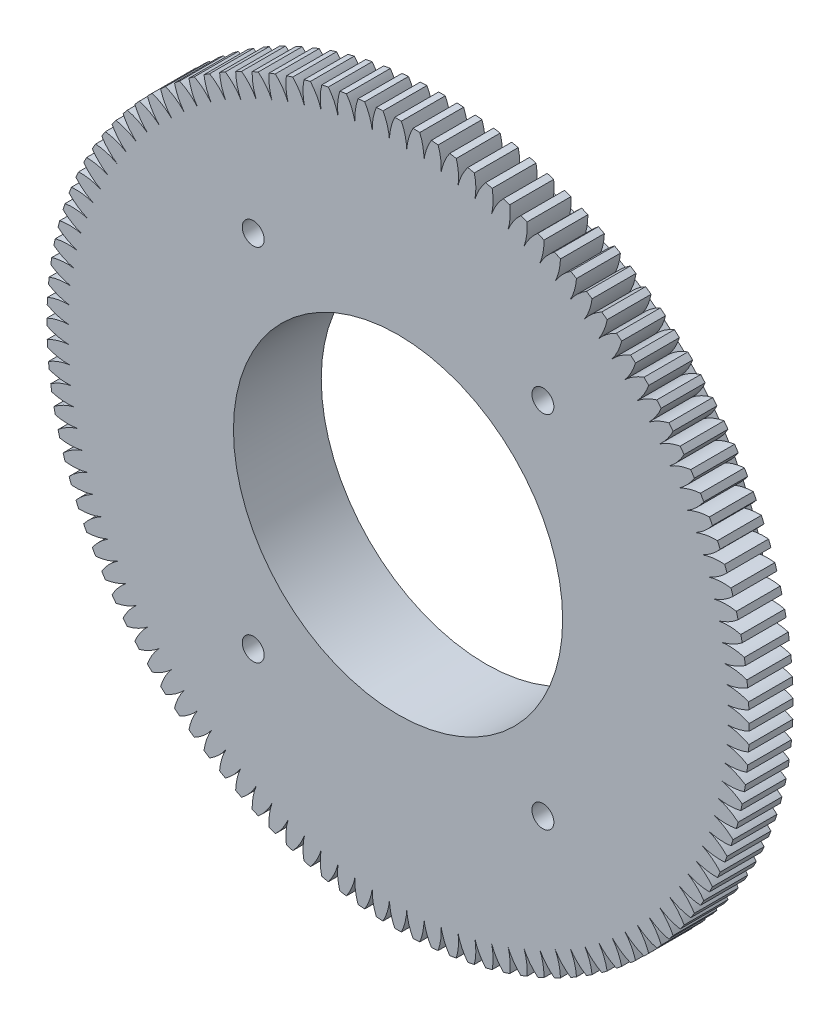
SolidWorks part; units mm, degrees
ref_plane "前视基准面" through (0, 0, 0) normal (0, 0, 1) x (1, 0, 0)
ref_plane "上视基准面" through (0, 0, 0) normal (0, 1, 0) x (1, 0, 0)
ref_plane "右视基准面" through (0, 0, 0) normal (1, 0, 0) x (0, 0, -1)
sketch "草图1" plane through (0, 0, 0) normal (0, 0, 1) x (1, 0, 0)
  circle A0 centre (0, 0) radius 75
  dimension "D1" = 150
extrude "凸台-拉伸1" add sketch "草图1" along normal blind 10
sketch "草图2" plane through (0, 0, 10) normal (0, 0, 1) x (1, 0, 0)
  line L1 (-33, -41) -> (33, -41) construction
  line L2 (-33, -41) -> (-33, 41) construction
  line L3 (-33, 41) -> (33, 41) construction
  line L4 (33, -41) -> (33, 41) construction
  line L5 (-33, -41) -> (33, 41) construction
  line L6 (-33, 41) -> (33, -41) construction
  point P0 (0, 0)
  dimension "D1" = 82
  dimension "D2" = 66
hole_wizard "M6 螺纹孔1" positions "草图3" profile "草图4" tap size "M6" standard "GB"
sketch "草图3" plane through (0, 0, 10) normal (0, 0, 1) x (1, 0, 0)
  point P0 (-33, 41)
  point P3 (33, 41)
  point P6 (33, -41)
  point P9 (-33, -41)
sketch "草图4" plane through (-33, 41, 10) normal (1, 0, 0) x (0, -1, 0)
  line L0 (0, 0) -> (0, 16.5022)
  line L1 (0, 16.5022) -> (2.5, 15)
  line L2 (2.5, 15) -> (2.5, 0)
  line L5 (2.5, 0) -> (0, 0)
  line L10 (0, 16.5022) -> (-2.5, 15) construction
  line L11 (0, -6.35) -> (0, 107.95) construction
  dimension "螺纹孔钻头直径" = 5
  dimension "螺纹孔钻头深度" = 15
  dimension "导头角度" = 118
cosmetic thread "孔螺纹线1" parameters "D1"=12, "D2"=6
cosmetic thread "孔螺纹线2" parameters "D1"=12, "D2"=6
cosmetic thread "孔螺纹线3" parameters "D1"=12, "D2"=6
cosmetic thread "孔螺纹线4" parameters "D1"=12, "D2"=6
sketch "草图5" plane through (0, 0, 10) normal (0, 0, 1) x (1, 0, 0)
  circle A0 centre (0, 0) radius 37.5
  dimension "D1" = 75
sketch "草图9" plane through (0, 0, 0) normal (0, 0, -1) x (-1, 0, 0)
  arc A5 (1.9633, 74.9743) -> (0.7613, 79.9964) centre (-10.3008, 74.6939) ccw
  arc A6 (-1.9633, 74.9743) -> (-0.7613, 79.9964) centre (10.3008, 74.6939) cw
  arc A7 (0.7613, 79.9964) -> (-0.7613, 79.9964) centre (0, 0) ccw
  circle A8 centre (0, 0) radius 75 construction
  arc A9 (1.9633, 74.9743) -> (-1.9633, 74.9743) centre (0, 0) ccw
extrude "凸台-拉伸2" add sketch "草图9" against normal blind 10
pattern_circular "阵列(圆周)1" count 120 over 360 about axis through (0, 0, 0) along (0, 0, 1) of "凸台-拉伸2"
sketch "草图11" plane through (0, 0, 0) normal (0, 0, -1) x (-1, 0, 0)
  circle A0 centre (0, 0) radius 70
  dimension "D1" = 140
sketch "草图13" plane through (0, 0, 0) normal (0, 0, -1) x (-1, 0, 0)
  circle A0 centre (0, 0) radius 65
  dimension "D1" = 130
extrude "凸台-拉伸3" add sketch "草图13" along normal blind 10
extrude "切除-拉伸1" cut sketch "草图5" against normal up to next
